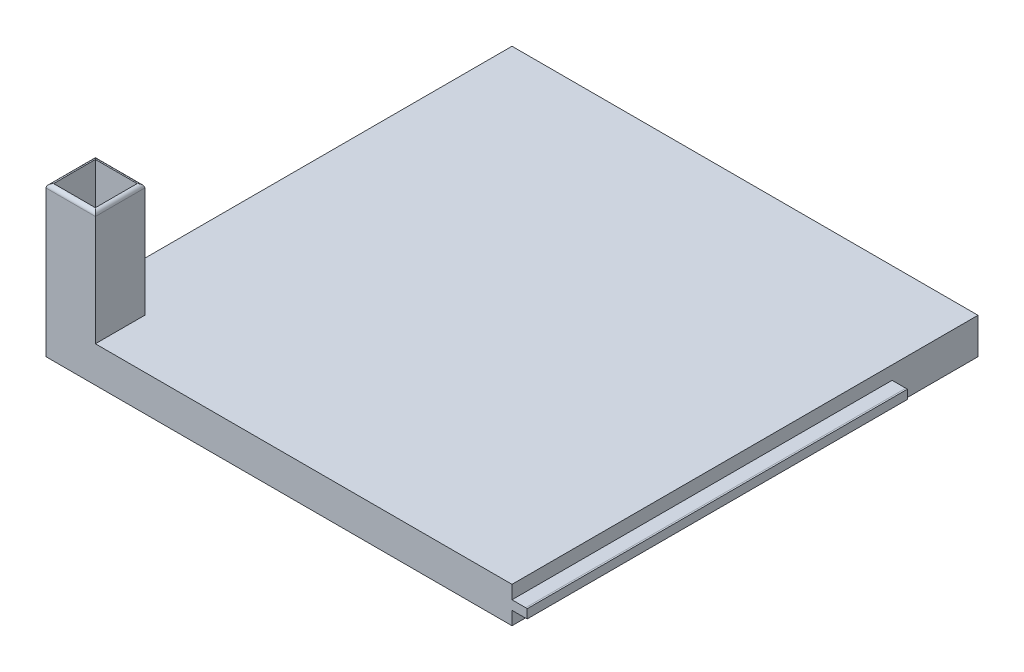
SolidWorks part; units mm, degrees
ref_plane "Front Plane" through (0, 0, 0) normal (0, 0, 1) x (1, 0, 0)
ref_plane "Top Plane" through (0, 0, 0) normal (0, 1, 0) x (1, 0, 0)
ref_plane "Right Plane" through (0, 0, 0) normal (1, 0, 0) x (0, 0, -1)
sketch "Sketch1" plane through (0, 0, 0) normal (0, 1, 0) x (1, 0, 0)
  line L1 (-22.3212, 15.875) -> (133.3788, 15.875)
  line L2 (-22.3212, 15.875) -> (-22.3212, -139.825)
  line L3 (-22.3212, -139.825) -> (133.3788, -139.825)
  line L4 (133.3788, 15.875) -> (133.3788, -139.825)
  line L5 (55.5288, -139.825) -> (55.5288, 15.875) construction
  line L6 (-22.3212, -61.975) -> (133.3788, -61.975) construction
  point P325 (-5.0492, -43.053)
  point P443 (-5.0492, -43.053)
  point P524 (55.5288, -61.975)
  dimension "D1" = 155.7
  dimension "D2" = 155.7
extrude "Boss-Extrude2" add sketch "Sketch1" along normal blind 12
sketch "Sketch2" plane through (0, 12, 0) normal (0, 1, 0) x (1, 0, 0)
  line L1 (-22.3212, -139.825) -> (-5.8212, -139.825)
  line L2 (-22.3212, -139.825) -> (-22.3212, -123.325)
  line L3 (-22.3212, -123.325) -> (-5.8212, -123.325)
  line L4 (-5.8212, -139.825) -> (-5.8212, -123.325)
  line L5 (-14.0712, -123.325) -> (-14.0712, -139.825) construction
  line L6 (-22.3212, -131.575) -> (-12.1612, -131.575) construction
  point P204 (-14.0712, -131.575)
  dimension "D1" = 16.5
  dimension "D2" = 16.5
extrude "Boss-Extrude3" add sketch "Sketch2" along normal blind 38.1
sketch "Sketch3" plane through (0, 0, 139.825) normal (0, 0, 1) x (1, 0, 0)
  line L0 (133.3788, 12) -> (133.3788, 0) construction
  line L1 (133.3788, 7.524) -> (138.4588, 7.524)
  line L2 (133.3788, 7.524) -> (133.3788, 4.476)
  line L3 (133.3788, 4.476) -> (138.4588, 4.476)
  line L4 (138.4588, 7.524) -> (138.4588, 4.476)
  line L5 (135.9188, 4.476) -> (135.9188, 7.524) construction
  line L6 (133.3788, 6) -> (138.4588, 6) construction
  line L7 (133.3788, 7.524) -> (133.3788, 12) construction
  line L8 (133.3788, 0) -> (135.9188, 4.476) construction
  line L9 (133.3788, 12) -> (135.9188, 7.524) construction
  point P1032 (135.9188, 6)
  dimension "D1" = 5.08
  dimension "D2" = 3.048
extrude "Boss-Extrude4" add sketch "Sketch3" against normal blind 127
chamfer "Chamfer1" distance 0.508 angle 4 1 edges at (138.4588, 7.524, 76.325) first distance on face at (135.9188, 7.524, 76.325)
chamfer "Chamfer2" distance 0.508 angle 4 1 edges at (138.4588, 4.476, 76.325) first distance on face at (135.9188, 4.476, 76.325)
sketch "Sketch4" plane through (-22.3212, 0, 0) normal (-1, 0, 0) x (0, 0, 1)
  line L0 (-15.875, 12) -> (-15.875, 0) construction
  line L1 (-15.875, 7.5875) -> (-10.541, 7.5875)
  line L2 (-15.875, 7.5875) -> (-15.875, 4.4125)
  line L3 (-15.875, 4.4125) -> (-10.541, 4.4125)
  line L4 (-10.541, 7.5875) -> (-10.541, 4.4125)
  line L5 (-13.208, 4.4125) -> (-13.208, 7.5875) construction
  line L6 (-15.875, 6) -> (-10.541, 6) construction
  line L7 (-15.875, 12) -> (-13.208, 7.5875) construction
  line L8 (-15.875, 0) -> (-13.208, 4.4125) construction
  point P456 (-13.208, 6)
  dimension "D1" = 5.334
  dimension "D2" = 3.175
  dimension "D3" = 5.1559
extrude "Cut-Extrude3" cut sketch "Sketch4" against normal blind 149.86 contours L2 L1 L4 L3
fillet "Fillet1" radius 1.27 4 edges at (-22.3212, 50.1, 131.575) (-14.0712, 50.1, 139.825) (-5.8212, 50.1, 131.575) (-14.0712, 50.1, 123.325) type face fillet first side face at (-14.0712, 50.1, 131.575) second side face at (-5.8212, 31.05, 131.575) second side face at (85.8375, 13.35, 139.825) second side face at (-22.3212, 14.82, 44.1718) second side face at (-14.0712, 31.05, 123.325)
sketch "Sketch5" plane through (0, 50.1, 0) normal (0, 1, 0) x (1, 0, 0)
  line L1 (-21.0512, -124.595) -> (-7.0912, -124.595)
  line L2 (-21.0512, -124.595) -> (-21.0512, -138.555)
  line L3 (-21.0512, -138.555) -> (-7.0912, -138.555)
  line L4 (-7.0912, -124.595) -> (-7.0912, -138.555)
  line L5 (-14.0712, -138.555) -> (-14.0712, -124.595) construction
  line L6 (-21.0512, -131.575) -> (-7.0912, -131.575) construction
  point P264 (-14.0712, -131.575)
extrude "Cut-Extrude4" cut sketch "Sketch5" against normal blind 38
